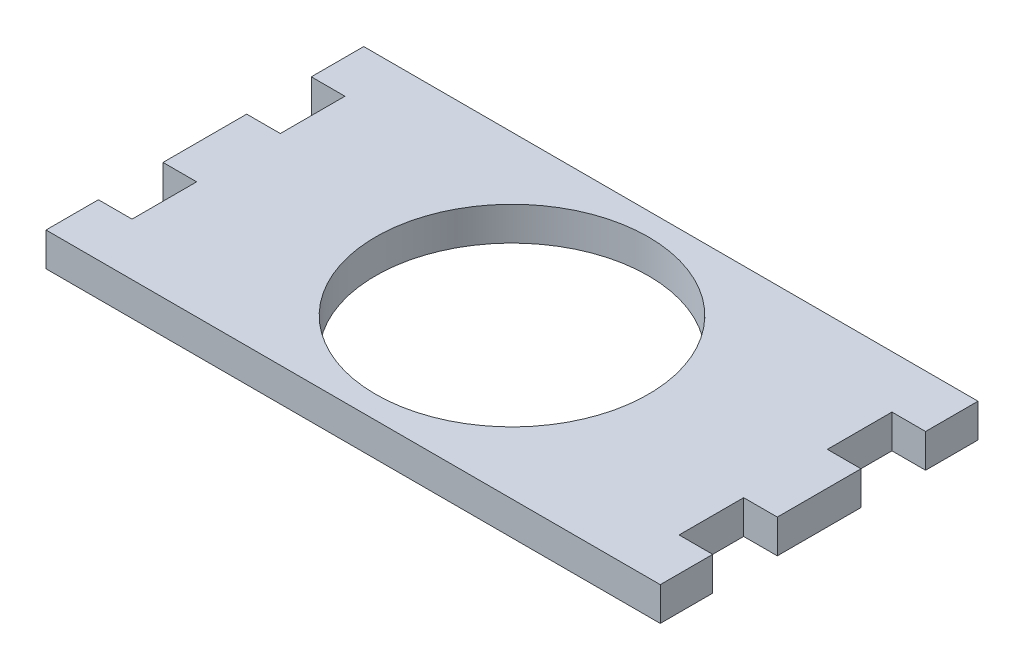
SolidWorks part; units mm, degrees
ref_plane "Front Plane" through (0, 0, 0) normal (0, 0, 1) x (1, 0, 0)
ref_plane "Top Plane" through (0, 0, 0) normal (0, 1, 0) x (1, 0, 0)
ref_plane "Right Plane" through (0, 0, 0) normal (1, 0, 0) x (0, 0, -1)
sketch "Sketch1" plane through (0, 0, 0) normal (0, 1, 0) x (1, 0, 0)
  line L0 (-29, 0) -> (0, 0) construction
  line L1 (-29, 15) -> (29, 15)
  line L2 (-29, 15) -> (-29, 10.05)
  line L3 (-29, -15) -> (29, -15)
  line L5 (0, 15) -> (0, -15) construction
  line L6 (29, -10.05) -> (29, -15)
  line L7 (29, -10.05) -> (25.825, -10.05)
  line L8 (-29, -10.05) -> (-25.825, -10.05)
  line L9 (-25.825, -10.05) -> (-25.825, -3.95)
  line L10 (-25.825, -3.95) -> (-29, -3.95)
  line L11 (-29, 3.95) -> (-29, -3.95)
  line L12 (-29, -10.05) -> (-29, -15)
  line L13 (-29, 10.05) -> (-25.825, 10.05)
  line L14 (-25.825, 10.05) -> (-25.825, 3.95)
  line L15 (-25.825, 3.95) -> (-29, 3.95)
  line L16 (25.825, -10.05) -> (25.825, -3.95)
  line L17 (25.825, -3.95) -> (29, -3.95)
  line L18 (29, 3.95) -> (29, -3.95)
  line L19 (25.825, 3.95) -> (29, 3.95)
  line L20 (25.825, 10.05) -> (25.825, 3.95)
  line L21 (29, 10.05) -> (25.825, 10.05)
  line L22 (29, 15) -> (29, 10.05)
  circle A0 centre (0, 0) radius 12.875
  dimension "D1" = 25.75
  dimension "D2" = 3.175
  dimension "D3" = 7.9
  dimension "D4" = 6.1
  dimension "D5" = 29
  dimension "D6" = 30
extrude "Boss-Extrude1" add sketch "Sketch1" along normal blind 3.175
